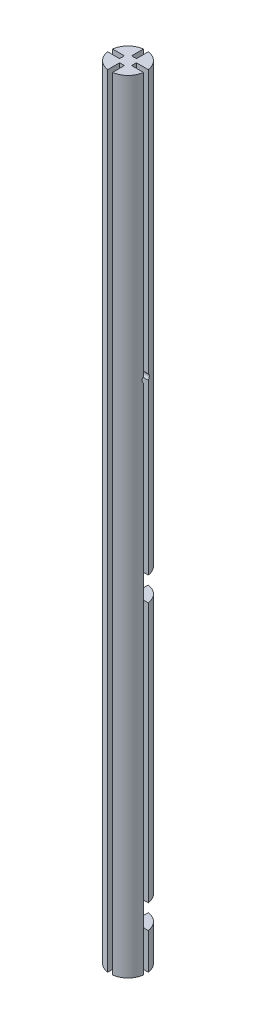
SolidWorks part; units mm, degrees
ref_plane "Front Plane" through (0, 0, 0) normal (0, 0, 1) x (1, 0, 0)
ref_plane "Top Plane" through (0, 0, 0) normal (0, 1, 0) x (1, 0, 0)
ref_plane "Right Plane" through (0, 0, 0) normal (1, 0, 0) x (0, 0, -1)
sketch "Sketch1" plane through (0, 0, 0) normal (0, 1, 0) x (1, 0, 0)
  line L5 (0, 194.8226) -> (0, 75) construction
  line L18 (-10, 74.3303) -> (-10, 25)
  line L19 (-10, 25) -> (10, 25)
  line L20 (10, 74.3303) -> (10, 25)
  line L21 (-29.2048, 0) -> (25.2155, 0) construction
  line L22 (74.3303, -10) -> (25, -10)
  line L23 (74.3303, 10) -> (25, 10)
  line L24 (25, 10) -> (25, -10)
  line L25 (-10, -74.3303) -> (-10, -25)
  line L26 (10, -74.3303) -> (10, -25)
  line L27 (10, -25) -> (-10, -25)
  line L28 (-74.3303, 10) -> (-25, 10)
  line L29 (-74.3303, -10) -> (-25, -10)
  line L30 (-25, -10) -> (-25, 10)
  line L31 (0, 75) -> (0, 25) construction
  line L32 (0, 25) -> (0, -243.8201) construction
  arc A2 (-10, 74.3303) -> (-74.3303, 10) centre (0, 0) ccw
  arc A3 (-74.3303, -10) -> (-10, -74.3303) centre (0, 0) ccw
  arc A4 (10, -74.3303) -> (74.3303, -10) centre (0, 0) ccw
  arc A5 (74.3303, 10) -> (10, 74.3303) centre (0, 0) ccw
  arc A6 (-10, 74.3303) -> (29.2889, 69.0446) centre (0, 0) cw
  point P1 (0, 25)
  point P4 (0, 93.7498)
  point P24 (-100, 0)
  point P29 (0, 0)
  point P30 (0, 0)
  dimension "D1" = 150
  dimension "D2" = 20
  dimension "D3" = 50
  dimension "D4" = 4
extrude "Boss-Extrude2" add sketch "Sketch1" along normal blind 4000 contours A2 L28 L30 L29 A3 L25 L27 L26 A4 L22 L24 L23 A5 L20 L19 L18
sketch "Sketch2" plane through (0, 0, 0) normal (0, 1, 0) x (1, 0, 0)
  line L0 (0, 74.3303) -> (0, 0)
  line L1 (74.3303, 74.3303) -> (74.3303, 0)
  line L2 (74.3303, 74.3303) -> (0, 74.3303)
  line L3 (74.3303, 0) -> (0, 0)
extrude "Cut-Extrude1" cut sketch "Sketch2" along normal mid plane 100 from offset 200
extrude "Cut-Extrude2" cut sketch "Sketch2<2>" against normal mid plane 100 from offset 1380
sketch "Sketch2<2>" plane through (0, 0, 0) normal (0, 1, 0) x (1, 0, 0) same geometry as "Sketch2"
ref_plane "Plane1" through (74.3303, 0, 0) normal (1, 0, 0) x (0, 0, -1)
ref_plane "Plane2" through (0, 0, -74.3303) normal (0, 0, -1) x (-1, 0, 0)
sketch "Sketch3" plane through (74.3303, 0, 0) normal (1, 0, 0) x (0, 0, -1)
  circle A0 centre (0, 2143) radius 15.2
extrude "Cut-Extrude3" cut sketch "Sketch3" against normal up to surface (49.3303 mm away) up to face at (25, 1193.3333, -3.3333)
sketch "Sketch4" plane through (0, 0, -74.3303) normal (0, 0, -1) x (-1, 0, 0)
  circle A2 centre (0, 2143) radius 15.2
extrude "Cut-Extrude4" cut sketch "Sketch4" against normal up to surface (49.3303 mm away) up to face at (3.3333, 1193.3333, -25)
sketch "Sketch5" plane through (0, 0, 25) normal (0, 0, 1) x (1, 0, 0)
  line L0 (-74.3303, 4000) -> (-74.3303, 3250)
  line L9 (-74.3303, 4000) -> (-74.3303, 0) construction
  line L10 (-74.3303, 3250) -> (74.3303, 3250)
  line L11 (74.3303, -16.72) -> (74.3303, 16.72) construction
  line L12 (74.3303, 3250) -> (74.3303, 4000)
  line L13 (74.3303, 4000) -> (74.3303, 2154.4473) construction
  line L14 (-74.3303, 4000) -> (74.3303, 4000)
extrude "Cut-Extrude5" cut sketch "Sketch5" against normal through all both and the other way through all
